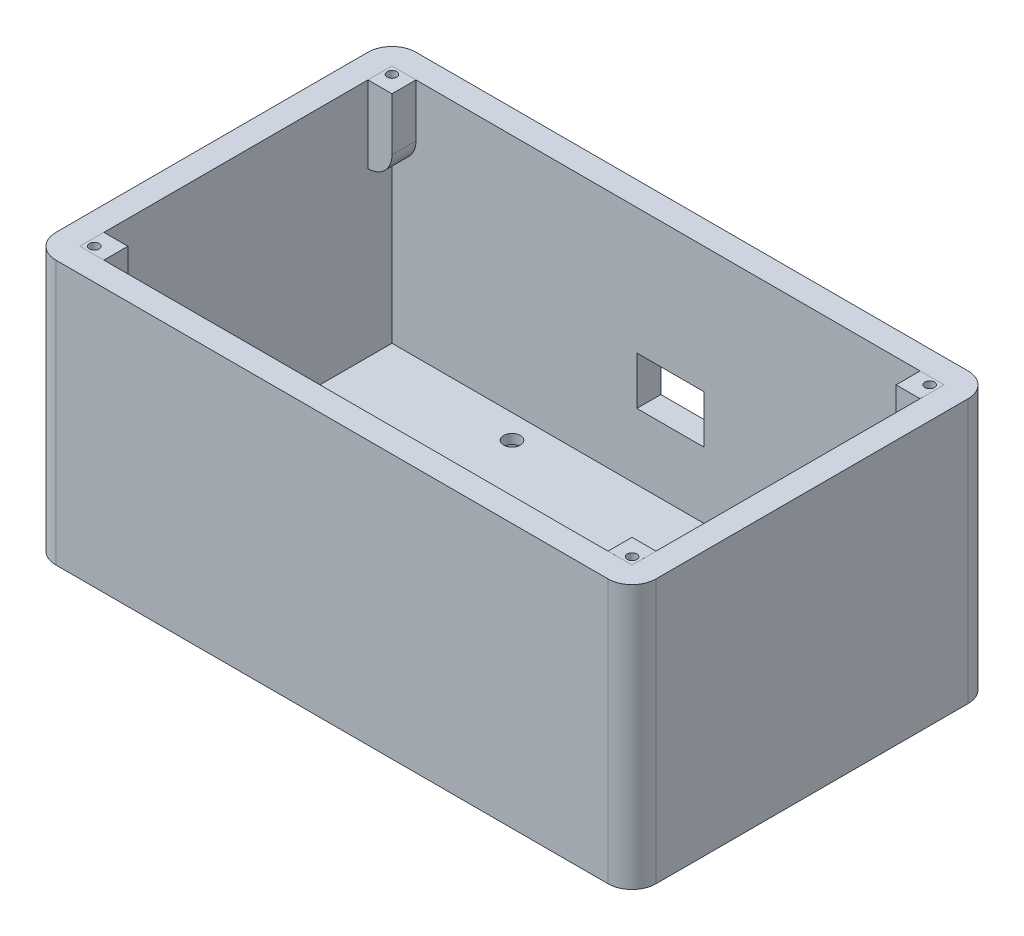
SolidWorks part; units mm, degrees
material "ABS"
ref_plane "Alzado" through (0, 0, 0) normal (0, 0, 1) x (1, 0, 0)
ref_plane "Planta" through (0, 0, 0) normal (0, 1, 0) x (1, 0, 0)
ref_plane "Vista lateral" through (0, 0, 0) normal (1, 0, 0) x (0, 0, -1)
sketch "Croquis1" plane through (0, 0, 0) normal (0, 1, 0) x (1, 0, 0)
  line L1 (-62.5, -37.5) -> (62.5, -37.5)
  line L2 (-62.5, -37.5) -> (-62.5, 37.5)
  line L3 (-62.5, 37.5) -> (62.5, 37.5)
  line L4 (62.5, -37.5) -> (62.5, 37.5)
  line L5 (-62.5, -37.5) -> (62.5, 37.5) construction
  line L6 (-62.5, 37.5) -> (62.5, -37.5) construction
  line L7 (-57.5, -32.5) -> (57.5, -32.5)
  line L8 (-57.5, -32.5) -> (-57.5, 32.5)
  line L9 (-57.5, 32.5) -> (57.5, 32.5)
  line L10 (57.5, -32.5) -> (57.5, 32.5)
  line L11 (-57.5, -32.5) -> (57.5, 32.5) construction
  line L12 (-57.5, 32.5) -> (57.5, -32.5) construction
  point P0 (0, 0)
  point P6 (0, 0)
  dimension "D1" = 65
  dimension "D2" = 5
  dimension "D3" = 115
  dimension "D4" = 5
extrude "Saliente-Extruir1" add sketch "Croquis1" along normal blind 50
sketch "Croquis2" plane through (0, 0, 0) normal (0, -1, 0) x (1, 0, 0)
  line L1 (-62.5, -37.5) -> (62.5, -37.5)
  line L2 (-62.5, -37.5) -> (-62.5, 37.5)
  line L3 (-62.5, 37.5) -> (62.5, 37.5)
  line L4 (62.5, -37.5) -> (62.5, 37.5)
  line L5 (-62.5, -37.5) -> (62.5, 37.5) construction
  line L6 (-62.5, 37.5) -> (62.5, -37.5) construction
  point P0 (0, 0)
extrude "Saliente-Extruir2" add sketch "Croquis2" along normal blind 5
fillet "Redondeo1" radius 5 4 edges at (-62.5, 22.5, 37.5) (62.5, 22.5, 37.5) (62.5, 22.5, -37.5) (-62.5, 22.5, -37.5)
sketch "Croquis3" plane through (0, 0, 0) normal (0, 1, 0) x (1, 0, 0)
  line L0 (53.5, 32.5) -> (53.5, -32.5) construction
  line L1 (57.5, 32.5) -> (-57.5, 32.5) construction
  line L2 (-57.5, -32.5) -> (57.5, -32.5) construction
  line L3 (57.5, -32.5) -> (57.5, 32.5) construction
  line L4 (57.5, 27.5) -> (-57.5, 27.5) construction
  line L5 (-57.5, 32.5) -> (-57.5, -32.5) construction
  line L6 (-27.5, 27.5) -> (-27.5, -32.5) construction
  line L7 (53.5, 24.1514) -> (56.4, 25.8257)
  line L8 (56.4, 25.8257) -> (56.4, 29.1743)
  line L9 (56.4, 29.1743) -> (53.5, 30.8486)
  line L10 (53.5, 30.8486) -> (50.6, 29.1743)
  line L11 (50.6, 29.1743) -> (50.6, 25.8257)
  line L12 (50.6, 25.8257) -> (53.5, 24.1514)
  line L13 (13, 27.5) -> (13, -32.5) construction
  line L14 (-24.6, 25.8257) -> (-27.5, 24.1514)
  line L15 (-24.6, 29.1743) -> (-24.6, 25.8257)
  line L16 (-27.5, 30.8486) -> (-24.6, 29.1743)
  line L17 (-30.4, 29.1743) -> (-27.5, 30.8486)
  line L18 (-30.4, 25.8257) -> (-30.4, 29.1743)
  line L19 (-27.5, 24.1514) -> (-30.4, 25.8257)
  line L20 (-27.5, -14.5) -> (53.5, -14.5) construction
  line L21 (-27.5, 6.5) -> (53.5, 6.5) construction
  line L22 (-24.6, -16.1743) -> (-24.6, -12.8257)
  line L23 (-27.5, -17.8486) -> (-24.6, -16.1743)
  line L24 (-30.4, -16.1743) -> (-27.5, -17.8486)
  line L25 (-30.4, -12.8257) -> (-30.4, -16.1743)
  line L26 (-27.5, -11.1514) -> (-30.4, -12.8257)
  line L27 (-24.6, -12.8257) -> (-27.5, -11.1514)
  line L28 (50.6, -12.8257) -> (53.5, -11.1514)
  line L29 (50.6, -16.1743) -> (50.6, -12.8257)
  line L30 (53.5, -17.8486) -> (50.6, -16.1743)
  line L31 (56.4, -16.1743) -> (53.5, -17.8486)
  line L32 (56.4, -12.8257) -> (56.4, -16.1743)
  line L33 (53.5, -11.1514) -> (56.4, -12.8257)
  circle A0 centre (53.5, 27.5) radius 2.9 construction
  point P12 (53.5, 27.5)
  dimension "D5" = 81
  dimension "D1" = 4
  dimension "D2" = 5
  dimension "D3" = 5
  dimension "D4" = 5.8
  dimension "D6" = 40.5
  dimension "D7" = 42
  dimension "D8" = 21
extrude "Saliente-Extruir3" add sketch "Croquis3" against normal blind 10
sketch "Croquis4" plane through (0, -10, 0) normal (0, -1, 0) x (1, 0, 0)
  line L6 (53.5, -24.1514) -> (50.6, -25.8257)
  line L7 (50.6, -25.8257) -> (50.6, -29.1743)
  line L8 (50.6, -29.1743) -> (53.5, -30.8486)
  line L9 (53.5, -30.8486) -> (56.4, -29.1743)
  line L10 (56.4, -29.1743) -> (56.4, -25.8257)
  line L11 (56.4, -25.8257) -> (53.5, -24.1514)
  line L12 (53.5, -24.1514) -> (50.6, -25.8257)
  line L13 (50.6, -25.8257) -> (50.6, -29.1743)
  line L14 (50.6, -29.1743) -> (53.5, -30.8486)
  line L15 (53.5, -30.8486) -> (56.4, -29.1743)
  line L16 (56.4, -29.1743) -> (56.4, -25.8257)
  line L17 (56.4, -25.8257) -> (53.5, -24.1514)
  line L18 (50.6, 16.1743) -> (50.6, 12.8257)
  line L19 (50.6, 12.8257) -> (53.5, 11.1514)
  line L20 (53.5, 11.1514) -> (56.4, 12.8257)
  line L21 (56.4, 12.8257) -> (56.4, 16.1743)
  line L22 (56.4, 16.1743) -> (53.5, 17.8486)
  line L23 (53.5, 17.8486) -> (50.6, 16.1743)
  line L24 (50.6, 16.1743) -> (50.6, 12.8257)
  line L25 (50.6, 12.8257) -> (53.5, 11.1514)
  line L26 (53.5, 11.1514) -> (56.4, 12.8257)
  line L27 (56.4, 12.8257) -> (56.4, 16.1743)
  line L28 (56.4, 16.1743) -> (53.5, 17.8486)
  line L29 (53.5, 17.8486) -> (50.6, 16.1743)
  line L30 (-24.6, 16.1743) -> (-27.5, 17.8486)
  line L31 (-27.5, 17.8486) -> (-30.4, 16.1743)
  line L32 (-30.4, 16.1743) -> (-30.4, 12.8257)
  line L33 (-30.4, 12.8257) -> (-27.5, 11.1514)
  line L34 (-27.5, 11.1514) -> (-24.6, 12.8257)
  line L35 (-24.6, 12.8257) -> (-24.6, 16.1743)
  line L36 (-24.6, 16.1743) -> (-27.5, 17.8486)
  line L37 (-27.5, 17.8486) -> (-30.4, 16.1743)
  line L38 (-30.4, 16.1743) -> (-30.4, 12.8257)
  line L39 (-30.4, 12.8257) -> (-27.5, 11.1514)
  line L40 (-27.5, 11.1514) -> (-24.6, 12.8257)
  line L41 (-24.6, 12.8257) -> (-24.6, 16.1743)
  line L42 (-24.6, -29.1743) -> (-24.6, -25.8257)
  line L43 (-24.6, -25.8257) -> (-27.5, -24.1514)
  line L44 (-27.5, -24.1514) -> (-30.4, -25.8257)
  line L45 (-30.4, -25.8257) -> (-30.4, -29.1743)
  line L46 (-30.4, -29.1743) -> (-27.5, -30.8486)
  line L47 (-27.5, -30.8486) -> (-24.6, -29.1743)
  line L48 (-24.6, -29.1743) -> (-24.6, -25.8257)
  line L49 (-24.6, -25.8257) -> (-27.5, -24.1514)
  line L50 (-27.5, -24.1514) -> (-30.4, -25.8257)
  line L51 (-30.4, -25.8257) -> (-30.4, -29.1743)
  line L52 (-30.4, -29.1743) -> (-27.5, -30.8486)
  line L53 (-27.5, -30.8486) -> (-24.6, -29.1743)
  dimension "D1" = 0
  dimension "D2" = 0
  dimension "D3" = 0
  dimension "D4" = 0
extrude "Cortar-Extruir1" cut sketch "Croquis4" against normal blind 8
sketch "Croquis6" plane through (0, -2, 0) normal (0, -1, 0) x (1, 0, 0)
  line L0 (53.5, -24.1514) -> (53.5, -30.8486) construction
  line L1 (-27.5, -30.8486) -> (-27.5, -24.1514) construction
  line L2 (-27.5, 17.8486) -> (-27.5, 11.1514) construction
  line L5 (53.5, 17.8486) -> (53.5, 11.1514) construction
  line L11 (-24.6, 12.8257) -> (-24.6, 16.1743)
  line L12 (-24.6, 16.1743) -> (-27.5, 17.8486)
  line L13 (-27.5, 17.8486) -> (-30.4, 16.1743)
  line L14 (-30.4, 16.1743) -> (-30.4, 12.8257)
  line L15 (-30.4, 12.8257) -> (-27.5, 11.1514)
  line L16 (-27.5, 11.1514) -> (-24.6, 12.8257)
  line L17 (-24.6, 12.8257) -> (-24.6, 16.1743)
  line L18 (-24.6, 16.1743) -> (-27.5, 17.8486)
  line L19 (-27.5, 17.8486) -> (-30.4, 16.1743)
  line L20 (-30.4, 16.1743) -> (-30.4, 12.8257)
  line L21 (-30.4, 12.8257) -> (-27.5, 11.1514)
  line L22 (-27.5, 11.1514) -> (-24.6, 12.8257)
  circle A0 centre (53.5, -27.5) radius 1.75
  circle A1 centre (-27.5, -27.5) radius 1.75
  circle A2 centre (-27.5, 14.5) radius 1.75
  circle A3 centre (53.5, 14.5) radius 1.75
  dimension "D1" = 3.5
  dimension "D2" = 3.5
  dimension "D4" = 3.5
  dimension "D5" = 3.5
  dimension "D3" = 0
extrude "Cortar-Extruir4" cut sketch "Croquis6" against normal up to surface (2 mm away) contours A0 | A1 | A2 | A3 up to face at (0, 0, 0)
sketch "Croquis7" plane through (0, 0, -32.5) normal (0, 0, 1) x (1, 0, 0)
  line L0 (1.5, 0) -> (1.5, 50) construction
  line L1 (57.5, 0) -> (-57.5, 0) construction
  line L2 (57.5, 50) -> (-57.5, 50) construction
  line L3 (57.5, 50) -> (57.5, 0) construction
  line L4 (-57.5, 19) -> (57.5, 19) construction
  line L5 (-57.5, 50) -> (-57.5, 0) construction
  line L7 (-3.9286, 23.75) -> (7.5, 23.75)
  line L9 (-5.1316, 13.75) -> (7.5, 13.75)
  line L10 (7.5, 23.75) -> (7.5, 13.75)
  line L11 (-3.9286, 23.75) -> (7.5, 13.75) construction
  line L12 (-5.1316, 13.75) -> (7.5, 23.75) construction
  line L15 (-3.9286, 23.75) -> (-6.5, 23.75)
  line L16 (-6.5, 23.75) -> (-6.5, 13.75)
  line L17 (-5.1316, 13.75) -> (-6.5, 13.75)
  point P12 (1.5, 19)
  point P14 (1.5, 19)
  dimension "D1" = 56
  dimension "D2" = 19
  dimension "D3" = 10
  dimension "D4" = 8
  dimension "D7" = 6
extrude "Cortar-Extruir5" cut sketch "Croquis7" against normal up to surface (5 mm away) up to face at (0, 22.5, -37.5)
sketch "Croquis8" plane through (0, 50, 0) normal (0, 1, 0) x (1, 0, 0)
  line L0 (-62.5, 27.5) -> (-52.5, 27.5)
  line L1 (-62.5, 32.5) -> (-62.5, -32.5) construction
  line L2 (-52.5, 27.5) -> (-52.5, 37.5)
  line L3 (57.5, 37.5) -> (-57.5, 37.5) construction
  line L4 (62.5, -32.5) -> (62.5, 32.5) construction
  line L5 (-57.5, -37.5) -> (57.5, -37.5) construction
  line L6 (62.5, -32.5) -> (62.5, 32.5)
  line L7 (-57.5, -37.5) -> (57.5, -37.5)
  line L8 (-62.5, 32.5) -> (-62.5, -32.5)
  line L9 (57.5, 37.5) -> (-57.5, 37.5)
  line L10 (0, 37.5) -> (0, -37.5) construction
  line L11 (0, 0) -> (62.5, 0) construction
  line L12 (62.5, 0) -> (-62.5, 0) construction
  line L13 (52.5, 27.5) -> (52.5, 37.5)
  line L14 (62.5, 27.5) -> (52.5, 27.5)
  line L15 (-62.5, -27.5) -> (-52.5, -27.5)
  line L16 (-52.5, -27.5) -> (-52.5, -37.5)
  line L17 (52.5, -27.5) -> (52.5, -37.5)
  line L18 (62.5, -27.5) -> (52.5, -27.5)
  line L19 (-57.5, 32.5) -> (-57.5, -32.5) construction
  line L20 (57.5, 32.5) -> (-57.5, 32.5) construction
  line L21 (57.5, -32.5) -> (57.5, 32.5) construction
  line L22 (-57.5, -32.5) -> (57.5, -32.5) construction
  line L23 (-57.5, 32.5) -> (-57.5, -32.5)
  line L24 (57.5, 32.5) -> (-57.5, 32.5)
  line L25 (57.5, -32.5) -> (57.5, 32.5)
  line L26 (-57.5, -32.5) -> (57.5, -32.5)
  arc A0 (62.5, 32.5) -> (57.5, 37.5) centre (57.5, 32.5) ccw construction
  arc A1 (57.5, -37.5) -> (62.5, -32.5) centre (57.5, -32.5) ccw construction
  arc A2 (-62.5, -32.5) -> (-57.5, -37.5) centre (-57.5, -32.5) ccw construction
  arc A3 (-57.5, 37.5) -> (-62.5, 32.5) centre (-57.5, 32.5) ccw construction
  arc A4 (62.5, 32.5) -> (57.5, 37.5) centre (57.5, 32.5) ccw
  arc A5 (57.5, -37.5) -> (62.5, -32.5) centre (57.5, -32.5) ccw
  arc A6 (-62.5, -32.5) -> (-57.5, -37.5) centre (-57.5, -32.5) ccw
  arc A7 (-57.5, 37.5) -> (-62.5, 32.5) centre (-57.5, 32.5) ccw
  line M20 (57.5, 32.5) -> (57.5, -32.5)
  line M21 (57.5, -32.5) -> (-57.5, -32.5)
  line M22 (-57.5, -32.5) -> (-57.5, 32.5)
  line M23 (-57.5, 32.5) -> (57.5, 32.5)
  dimension "D4" = 10
  dimension "D5" = 10
extrude "Saliente-Extruir4" add sketch "Croquis8" along normal blind 0.001 and the other way blind 16 contours L16 L15 M22 M21 | L18 L17 M20 M21 | L14 L13 M20 M23 | L0 L2 M23 M22 region at (-55, 50, -30) region at (-55, 50, 30) region at (55, 50, -30) region at (55, 50, 30)
fillet "Redondeo2" radius 5 4 edges at (-52.5, 34, -30) (-52.5, 34, 30) (52.5, 34, 30) (52.5, 34, -30)
sketch "Croquis9" plane through (0, 50.001, 0) normal (0, 1, 0) x (1, 0, 0)
  line L0 (-62.5, 32.5) -> (-62.5, -32.5) construction
  line L1 (57.5, 37.5) -> (-57.5, 37.5) construction
  line L2 (-62.5, 32.5) -> (-62.5, -32.5)
  line L3 (57.5, 37.5) -> (-57.5, 37.5)
  line L4 (0, 37.5) -> (0, -36.8665) construction
  line L5 (-62.5, 0) -> (63.0471, 0) construction
  circle A0 centre (-56, 31) radius 1
  circle A1 centre (56, 31) radius 1
  circle A2 centre (56, -31) radius 1
  circle A3 centre (-56, -31) radius 1
  dimension "D1" = 6.5
  dimension "D3" = 2
  dimension "D2" = 6.5
hole_wizard "Diámetro de taladro Ø2.0 (2)4" positions "Croquis3D2" profile "Croquis10" hole size "Ø2.0" standard "Ansi Metric"
sketch3d "Croquis3D2"
  point P0 (-56, 50.001, -31)
  point P3 (56, 50.001, -31)
  point P6 (56, 50.001, 31)
  point P9 (-56, 50.001, 31)
sketch "Croquis10" plane through (-56, 50.001, -31) normal (1, 0, 0) x (0, 0, 1)
  line L0 (0, 0) -> (0, 10.6009)
  line L1 (0, 10.6009) -> (1, 10)
  line L2 (1, 10) -> (1, 0)
  line L5 (1, 0) -> (0, 0)
  line L10 (0, 10.6009) -> (-1, 10) construction
  line L11 (0, -6.35) -> (0, 107.95) construction
  dimension "Diámetro de taladro" = 2
  dimension "Profundidad de taladro" = 10
  dimension "Ángulo de perforador" = 118
sketch "Croquis11" plane through (0, 0, 0) normal (0, 1, 0) x (1, 0, 0)
  line L0 (-57.5, -32.5) -> (57.5, -32.5) construction
  line L1 (57.5, -32.5) -> (57.5, 32.5) construction
  circle A0 centre (12.5, -24) radius 2.5
  circle A1 centre (48.5, -24) radius 2.5
  dimension "D1" = 5
  dimension "D2" = 5
  dimension "D3" = 36
  dimension "D6" = 8.5
  dimension "D4" = 8.5
  dimension "D5" = 9
sketch "Croquis12" plane through (0, 0, -32.5) normal (0, 0, 1) x (1, 0, 0)
  line L0 (57.5, 34) -> (57.5, 0) construction
  circle A0 centre (48.5, 20.9291) radius 1.5
  circle A1 centre (12.5, 20.9291) radius 1.5
  dimension "D1" = 3
  dimension "D2" = 3
  dimension "D4" = 36
  dimension "D3" = 9
extrude "Saliente-Extruir5" add sketch "Croquis11" along normal blind 4
sketch "Croquis13" plane through (0, 4, 0) normal (0, 1, 0) x (1, 0, 0)
  circle A0 centre (12.5, -24) radius 1.5
  circle A1 centre (48.5, -24) radius 1.5
  dimension "D1" = 3
  dimension "D2" = 3
extrude "Cortar-Extruir6" cut sketch "Croquis13" against normal up to surface (9 mm away) up to face at (53.5, -5, 14.5)
sketch "Croquis14" plane through (0, -5, 0) normal (0, -1, 0) x (1, 0, 0)
  line L0 (12.5, 25.5) -> (12.5, 22.5) construction
  line L1 (48.5, 25.5) -> (48.5, 22.5) construction
  line L3 (12.5, 20.6514) -> (15.4, 22.3257)
  line L4 (15.4, 22.3257) -> (15.4, 25.6743)
  line L5 (15.4, 25.6743) -> (12.5, 27.3486)
  line L6 (12.5, 27.3486) -> (9.6, 25.6743)
  line L7 (9.6, 25.6743) -> (9.6, 22.3257)
  line L8 (9.6, 22.3257) -> (12.5, 20.6514)
  line L9 (48.5, 20.6514) -> (51.4, 22.3257)
  line L10 (51.4, 22.3257) -> (51.4, 25.6743)
  line L11 (51.4, 25.6743) -> (48.5, 27.3486)
  line L12 (48.5, 27.3486) -> (45.6, 25.6743)
  line L13 (45.6, 25.6743) -> (45.6, 22.3257)
  line L14 (45.6, 22.3257) -> (48.5, 20.6514)
  circle A0 centre (12.5, 24) radius 1.5 construction
  circle A1 centre (48.5, 24) radius 1.5 construction
  circle A2 centre (12.5, 24) radius 2.9 construction
  circle A3 centre (48.5, 24) radius 2.9 construction
  point P19 (11.05, 26.5115)
  dimension "D1" = 5.8
  dimension "D2" = 5.8
extrude "Cortar-Extruir7" cut sketch "Croquis14" against normal blind 3.2
